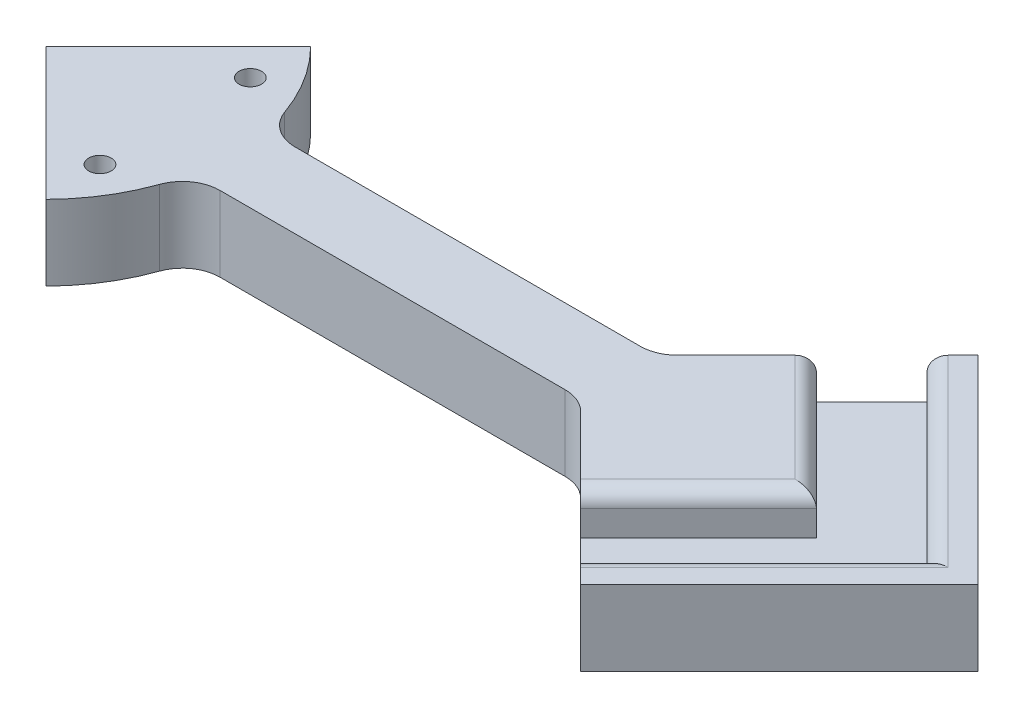
SolidWorks part; units mm, degrees
ref_plane "Front Plane" through (0, 0, 0) normal (0, 0, 1) x (1, 0, 0)
ref_plane "Top Plane" through (0, 0, 0) normal (0, 1, 0) x (1, 0, 0)
ref_plane "Right Plane" through (0, 0, 0) normal (1, 0, 0) x (0, 0, -1)
sketch "Sketch5" plane through (0, 0, 0) normal (0, 1, 0) x (1, 0, 0)
  line L0 (193.4968, 0) -> (0, 0) construction
  line L1 (0, 0) -> (69.85, 69.85) construction
  circle A0 centre (0, 0) radius 162.2828 construction
  circle A1 centre (69.85, 69.85) radius 63.5 construction
  circle A2 centre (69.85, -69.85) radius 63.5 construction
  circle A3 centre (-69.85, -69.85) radius 63.5 construction
  circle A4 centre (-69.85, 69.85) radius 63.5 construction
  point P15 (0, 0)
  dimension "D1" = 324.5656
  dimension "D2" = 127
  dimension "D3" = 45
  dimension "D4" = 4
sketch "Sketch8" plane through (0, 0, 0) normal (0, 0, 1) x (1, 0, 0)
  line L0 (0, 34.2637) -> (0, -61.9336) construction
sketch "Sketch11" plane through (0, 0, 0) normal (0, 1, 0) x (1, 0, 0)
  line L0 (0, 137.9723) -> (0, -128.7054) construction
  line L1 (-137.9723, 0) -> (137.9723, 0) construction
  line L2 (0, 0) -> (88.3597, 88.3597) construction
  dimension "D1" = 45
sketch "Sketch12" plane through (0, 0, 0) normal (0, 1, 0) x (1, 0, 0)
  line L0 (193.4968, 0) -> (0, 0) construction
  line L3 (139.8796, 6.35) -> (6.5296, 6.35)
  line L4 (6.5296, 6.35) -> (0.1796, 0)
  line L5 (0.1796, 0) -> (6.5296, -6.35)
  line L6 (6.5296, -6.35) -> (139.8796, -6.35)
  line L7 (139.8796, -6.35) -> (139.8796, 6.35)
  line L8 (0, 0) -> (69.85, 69.85) construction
  circle A28 centre (69.85, 69.85) radius 63.5 construction
  circle A33 centre (69.85, -69.85) radius 63.5 construction
  point P11 (0, 0)
  point P13 (0, 0)
  point P14 (0, 0)
  point P16 (0, 0)
  point P19 (0, 0)
  point P20 (0, 0)
  dimension "D2" = 4
  dimension "D1" = 0.127
  dimension "D5" = 133.35
extrude "Boss-Extrude11" add sketch "Sketch12" along normal blind 12.7
sketch "Sketch23" plane through (0, 0, 0) normal (0, 1, 0) x (1, 0, 0)
  line L0 (69.85, 69.85) -> (139.7, 0) construction
  line L1 (193.4968, 0) -> (0, 0) construction
  line L2 (90.521, 0) -> (124.0907, 33.5698)
  line L3 (157.6605, 0) -> (124.0907, -33.5698)
  line L4 (124.0907, -33.5698) -> (90.521, 0)
  line L5 (124.0907, 33.5698) -> (157.6605, 0)
  line L7 (0, 0) -> (69.85, 69.85) construction
  dimension "D1" = 12.7
  dimension "D2" = 64.008
extrude "Boss-Extrude12" add sketch "Sketch23" along normal up to surface (12.7 mm away) up to face at (58.5996, 12.7, 0)
sketch "Sketch26" plane through (0, 0, 0) normal (0, 1, 0) x (1, 0, 0)
  line L0 (22.5403, 22.3607) -> (0.1796, 0)
  line L1 (193.4968, 0) -> (0, 0) construction
  line L2 (0.1796, 0) -> (22.5403, -22.3607)
  line L3 (0, 0) -> (69.85, 69.85) construction
  line L4 (6.5296, 6.35) -> (0.1796, 0) construction
  arc A0 (22.5403, -22.3607) -> (22.5403, 22.3607) centre (0, 0) ccw
  dimension "D1" = 63.5
extrude "Boss-Extrude13" add sketch "Sketch26" along normal up to surface (12.7 mm away) up to face at (76.6028, 12.7, 0)
sketch "Sketch24" plane through (0, 0, 0) normal (0, 1, 0) x (1, 0, 0)
  line L0 (119.7802, 29.2592) -> (149.0395, 0)
  line L1 (124.0907, 33.5698) -> (96.871, 6.35) construction
  line L2 (193.4968, 0) -> (0, 0) construction
  line L3 (149.0395, 0) -> (119.7802, -29.2592)
  line L4 (96.871, -6.35) -> (124.0907, -33.5698) construction
  line L5 (119.7802, -29.2592) -> (110.4408, -19.9198)
  line L6 (110.4408, -19.9198) -> (130.3605, 0)
  line L7 (130.3605, 0) -> (110.4408, 19.9198)
  line L8 (110.4408, 19.9198) -> (119.7802, 29.2592)
  line L11 (115.1105, 24.5895) -> (144.3697, -4.6697) construction
  line L12 (157.6605, 0) -> (124.0907, 33.5698) construction
  dimension "D1" = 12.7
  dimension "D2" = 13.208
extrude "Cut-Extrude1" cut sketch "Sketch24" against normal blind 6.858 from surface starting at face at (70.9399, 12.7, 0)
sketch "Sketch25" plane through (0, 0, 0) normal (0, 1, 0) x (1, 0, 0)
  line L0 (193.4968, 0) -> (0, 0) construction
  line L1 (0, 0) -> (21.997, 12.7) construction
  line L2 (0, 0) -> (58.3902, 0) construction
  circle A1 centre (21.997, 12.7) radius 1.9
  circle A2 centre (21.997, -12.7) radius 1.9
  dimension "D1" = 3.8
  dimension "D4" = 25.4
  dimension "D5" = 30
extrude "Cut-Extrude2" cut sketch "Sketch25" along normal through all
fillet "Fillet1" radius 2.54 4 edges at (134.4098, 12.7, 14.6296) (134.4098, 12.7, -14.6296) (120.4006, 12.7, -9.9599) (120.4006, 12.7, 9.9599)
fillet "Fillet2" radius 6.35 4 edges at (96.871, 6.35, -6.35) (96.871, 6.35, 6.35) (31.1085, 6.35, -6.35) (31.1085, 6.35, 6.35)
equation "\"cage spacing\"= 0.5'space between cages"
equation "\"cage diameter\" = 5'cage diameter"
equation "\"cage radius\"= \"cage diameter\" / 2'cage radius"
equation "\"D1@Sketch5\"=2*(2^0.5*(\"cage radius\"+\"cage spacing\"/2)+\"cage radius\")"
equation "\"tightTol\" = 0.005in"
equation "\"normTol\"= 0.01in"
equation "\"looseTol\"= 0.02in"
equation "\"D2@Sketch5\"=\"cage diameter\""
equation "\"D2@Sketch23\"=\"cage radius\"+\"looseTol\""
equation "\"D2@Sketch24\"=\"looseTol\"+0.5"
equation "\"D1@Cut-Extrude1\"=\"looseTol\"+0.25"
equation "\"D1@Sketch25\"=3.8mm"
